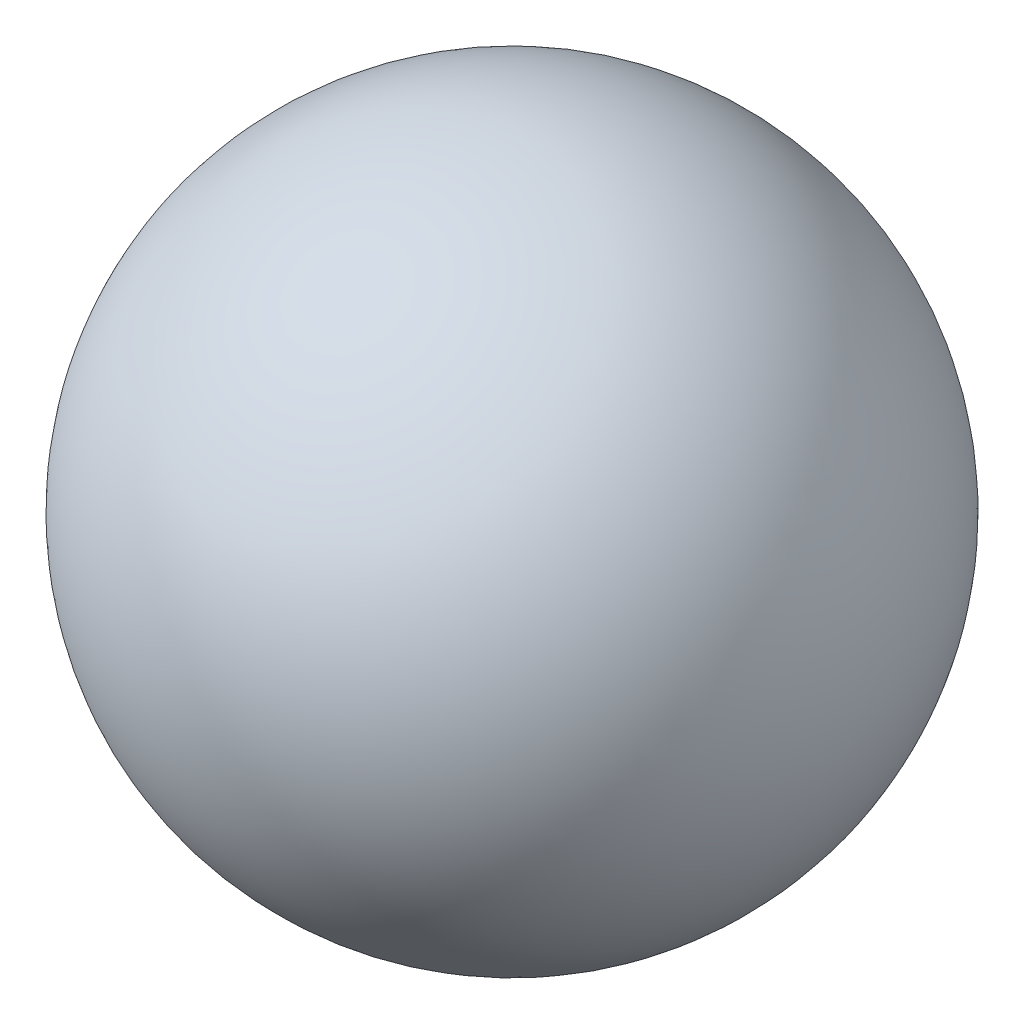
SolidWorks part; units mm, degrees
ref_plane "Front Plane" through (0, 0, 0) normal (0, 0, 1) x (1, 0, 0)
ref_plane "Top Plane" through (0, 0, 0) normal (0, 1, 0) x (1, 0, 0)
ref_plane "Right Plane" through (0, 0, 0) normal (1, 0, 0) x (0, 0, -1)
sketch "Sketch1" plane through (0, 0, 0) normal (0, 1, 0) x (1, 0, 0)
  line L0 (-4.5, 0) -> (4.5, 0)
  arc A0 (4.5, 0) -> (-4.5, 0) centre (0, 0) ccw
  dimension "D1" = 4.5
revolve "Revolve1" add sketch "Sketch1" angle 360 about L0
ref_axis "Axis1" through (-4.95, 0, 0) along (1, 0, 0)
